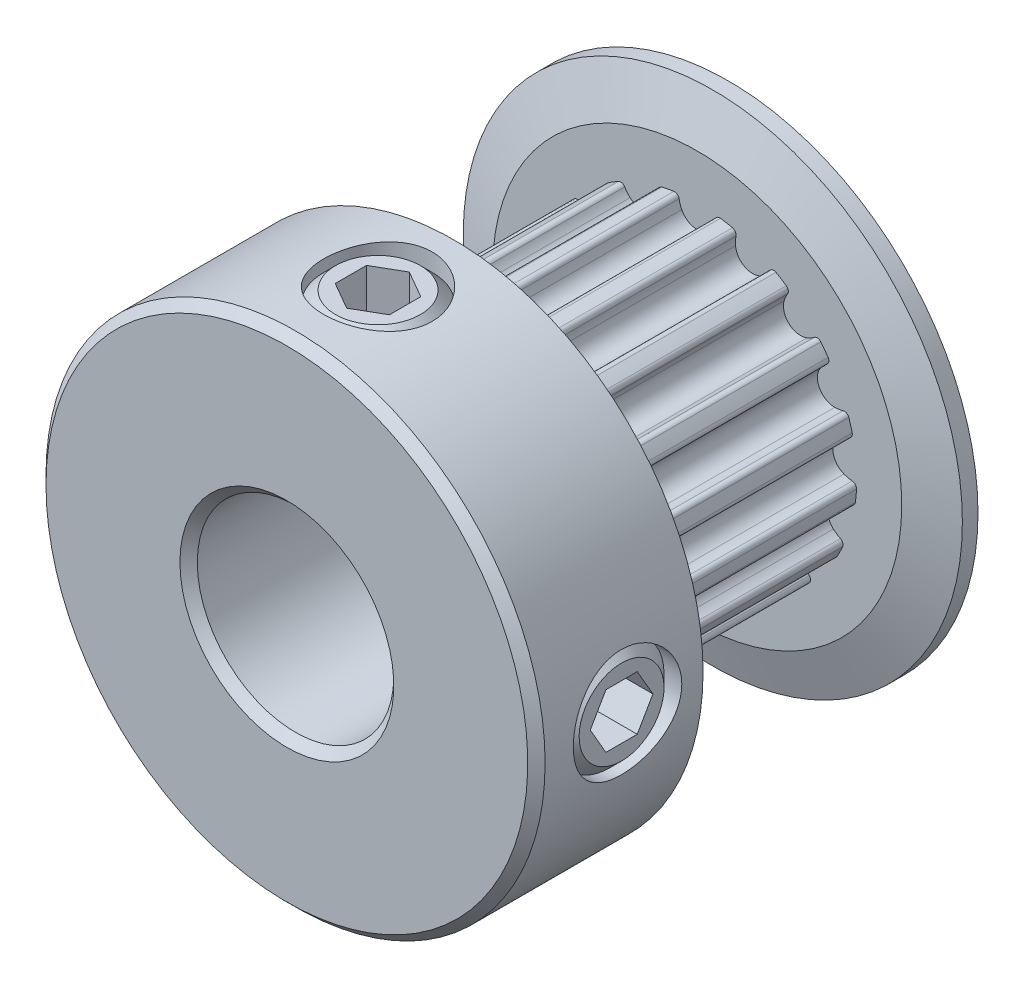
SolidWorks part; units mm, degrees
ref_plane "Front Plane" through (0, 0, 0) normal (0, 0, 1) x (1, 0, 0)
ref_plane "Top Plane" through (0, 0, 0) normal (0, 1, 0) x (1, 0, 0)
ref_plane "Right Plane" through (0, 0, 0) normal (1, 0, 0) x (0, 0, -1)
sketch "Sketch1" plane through (0, 0, 0) normal (0, 0, 1) x (1, 0, 0)
  line L1 (-1.7182, 4.406) -> (1.7182, 4.406) construction
  line L4 (0, 0) -> (0, 4.406) construction
  line L5 (0, 4.406) -> (0, 10.5496) construction
  line L6 (0, 5.41) -> (1.9655, 5.0403) construction
  line L7 (1.9655, 5.0403) -> (2.5999, 4.793) construction
  line L8 (1.9655, 5.0403) -> (1.7182, 4.406) construction
  line L9 (-1.9655, 5.0403) -> (-1.7182, 4.406) construction
  line L10 (-1.8733, 4.8037) -> (-3.1449, 8.0645)
  line L11 (-3.1449, 8.0645) -> (3.1449, 8.0645)
  line L12 (3.1449, 8.0645) -> (1.8733, 4.8037)
  circle A0 centre (0, 0) radius 5.41 construction
  circle A1 centre (0, 0) radius 8.0645 construction
  circle A2 centre (0, 0) radius 5.156 construction
  arc A3 (-0.4989, 4.7178) -> (0.4989, 4.7178) centre (0, 4.961) ccw
  arc A4 (-0.4989, 4.7178) -> (-0.5842, 4.9788) centre (0.4, 5.156) cw
  arc A5 (-1.8733, 4.8037) -> (-0.7537, 5.1006) centre (0, 0) cw
  arc A6 (-0.5842, 4.9788) -> (-0.7537, 5.1006) centre (-0.7318, 4.9522) ccw
  arc A7 (1.8733, 4.8037) -> (0.7537, 5.1006) centre (0, 0) ccw
  arc A8 (0.5842, 4.9788) -> (0.7537, 5.1006) centre (0.7318, 4.9522) cw
  arc A9 (0.4989, 4.7178) -> (0.5842, 4.9788) centre (-0.4, 5.156) ccw
  point P6 (0, 20.9083)
  point P11 (0, 5.41)
  point P13 (0, 8.0645)
  point P14 (0, 5.156)
  dimension "D1" = 10.3587
  dimension "D2" = 5.1396
sketch "Sketch2" plane through (0, 0, 0) normal (1, 0, 0) x (0, 0, -1)
  line L0 (-7.135, 3.175) -> (7.135, 3.175)
  line L1 (-7.135, 3.175) -> (-7.135, 8.0645)
  line L2 (-1.75, 8.0645) -> (-7.135, 8.0645)
  line L3 (-2.255, 3.175) -> (-2.255, 8.0645) construction
  line L4 (-2.255, 8.0645) -> (-1.245, 8.0645) construction
  line L5 (-1.245, 8.0645) -> (-1.245, 5.156) construction
  line L6 (-1.245, 5.156) -> (6.125, 5.156)
  line L7 (6.125, 5.156) -> (6.125, 8.0645) construction
  line L8 (6.125, 8.0645) -> (7.135, 8.0645) construction
  line L9 (7.135, 8.0645) -> (7.135, 3.175)
  line L10 (-7.135, 0) -> (7.135, 0) construction
  line L11 (6.63, 8.0645) -> (6.125, 6.6102)
  line L12 (-1.245, 6.6102) -> (-1.75, 8.0645)
  line L14 (-1.245, 6.6102) -> (-1.245, 5.156)
  line L15 (6.125, 5.156) -> (6.125, 6.6102)
  line L16 (6.63, 8.0645) -> (7.135, 8.0645)
  arc A0 (-1.245, 6.6102) -> (-1.75, 8.0645) centre (-3.5914, 6.6102) ccw construction
  arc A1 (6.125, 6.6102) -> (6.63, 8.0645) centre (8.4714, 6.6102) cw construction
  point P12 (-1.245, 6.6102)
  point P14 (-1.75, 8.0645)
  point P20 (6.125, 6.6102)
  point P21 (6.63, 8.0645)
  point P25 (6.125, 0)
  point P26 (-1.245, 0)
  dimension "OA" = 14.27
  dimension "Bore" = 6.35
  dimension "Outside Width" = 8.38
  dimension "Inside Width" = 7.37
revolve "Revolve1" add sketch "Sketch2" angle 360 mid plane about L10
sketch "Sketch3" plane through (0, 0, 0) normal (0, 0, 1) x (1, 0, 0)
  line L6 (3.1449, 8.0645) -> (-3.1449, 8.0645)
  line L7 (1.8733, 4.8037) -> (3.1449, 8.0645)
  line L8 (-3.1449, 8.0645) -> (-1.8733, 4.8037)
  line L9 (3.1449, 8.0645) -> (-3.1449, 8.0645)
  line L10 (1.8733, 4.8037) -> (3.1449, 8.0645)
  line L11 (-3.1449, 8.0645) -> (-1.8733, 4.8037)
  arc A8 (1.8733, 4.8037) -> (0.7537, 5.1006) centre (0, 0) ccw
  arc A9 (0.7537, 5.1006) -> (0.5842, 4.9788) centre (0.7318, 4.9522) ccw
  arc A10 (0.4989, 4.7178) -> (0.5842, 4.9788) centre (-0.4, 5.156) ccw
  arc A11 (-0.4989, 4.7178) -> (0.4989, 4.7178) centre (0, 4.961) ccw
  arc A12 (-0.5842, 4.9788) -> (-0.4989, 4.7178) centre (0.4, 5.156) ccw
  arc A13 (-0.5842, 4.9788) -> (-0.7537, 5.1006) centre (-0.7318, 4.9522) ccw
  arc A14 (-0.7537, 5.1006) -> (-1.8733, 4.8037) centre (0, 0) ccw
  arc A15 (1.8733, 4.8037) -> (0.7537, 5.1006) centre (0, 0) ccw
  arc A16 (0.7537, 5.1006) -> (0.5842, 4.9788) centre (0.7318, 4.9522) ccw
  arc A17 (0.4989, 4.7178) -> (0.5842, 4.9788) centre (-0.4, 5.156) ccw
  arc A18 (-0.4989, 4.7178) -> (0.4989, 4.7178) centre (0, 4.961) ccw
  arc A19 (-0.5842, 4.9788) -> (-0.4989, 4.7178) centre (0.4, 5.156) ccw
  arc A20 (-0.5842, 4.9788) -> (-0.7537, 5.1006) centre (-0.7318, 4.9522) ccw
  arc A21 (-0.7537, 5.1006) -> (-1.8733, 4.8037) centre (0, 0) ccw
  dimension "D1" = 0
extrude "Cut-Extrude1" cut sketch "Sketch3" against normal up to vertex (6.125 mm away) from vertex up to point (0, 5.156, -6.125) starting at point (0, 5.156, 1.245)
pattern_circular "CirPattern1" count 17 over 360 about axis through (0, 0, 7.135) along (0, 0, 1) of "Cut-Extrude1"
sketch "Sketch4" plane through (0, 0, 0) normal (1, 0, 0) x (0, -1, 0)
  line L0 (0, -1.245) -> (0, -7.135) construction
  line L1 (-3.175, -7.135) -> (3.175, -7.135) construction
  line L2 (6.6102, -1.245) -> (-6.6102, -1.245) construction
  circle A0 centre (0, -4.19) radius 1.7526
extrude "Cut-Extrude2" cut sketch "Sketch4" along normal through all
ref_plane "Plane1" through (0, 0, 4.19) normal (0, 0, 1) x (1, 0, 0)
sketch "Sketch5" plane through (0, 0, 4.19) normal (0, 0, 1) x (1, 0, 0)
  line L0 (0, 0) -> (0, 8.0645) construction
  line L1 (3.175, -1.3716) -> (3.175, 0)
  line L2 (3.556, -1.7526) -> (7.4908, -1.7526)
  line L3 (3.175, 0) -> (8.0645, 0) construction
  line L4 (3.175, 0) -> (7.8718, 0)
  line L5 (7.8718, 0) -> (7.8718, -1.3716)
  line L6 (3.556, -1.7526) -> (3.175, -1.3716)
  line L7 (7.8718, -1.3716) -> (7.4908, -1.7526)
  circle A0 centre (0, 0) radius 8.0645 construction
  circle A1 centre (0, 0) radius 3.175 construction
  point P2 (3.175, -1.7526)
  point P11 (7.8718, -1.7526)
revolve "Revolve2" add sketch "Sketch5" angle 360 mid plane about L4
sketch "Sketch6" plane through (7.8718, 5.3841, 0) normal (-1, 0, 0) x (0, -1, 0)
  line L1 (5.3841, 5.2019) -> (4.5078, 4.6959)
  line L2 (4.5078, 4.6959) -> (4.5078, 3.6841)
  line L3 (4.5078, 3.6841) -> (5.3841, 3.1781)
  line L4 (5.3841, 3.1781) -> (6.2604, 3.6841)
  line L5 (6.2604, 3.6841) -> (6.2604, 4.6959)
  line L6 (6.2604, 4.6959) -> (5.3841, 5.2019)
  circle A0 centre (5.3841, 4.19) radius 0.8763 construction
  dimension "D1" = 1.7526
extrude "Cut-Extrude3" cut sketch "Sketch6" along normal blind 1.3144
pattern_circular "CirPattern3" count 2 over 90 about axis through (0, 0, 7.135) along (0, 0, 1) of "Cut-Extrude2", "Revolve2", "Cut-Extrude3"
chamfer "Chamfer1" distance 0.2807 angle 45 2 edges at (3.175, 0, 7.135) (8.0645, 0, 7.135)
ref_axis "Center Axis 1" through (0, 0, -7.135) along (0, 0, 1)
ref_plane "Contact Plane 1" through (0, 0, 7.135) normal (0, 0, 1) x (1, 0, 0)
ref_plane "Contact Plane 2" through (0, 0, -7.135) normal (0, 0, -1) x (-1, 0, 0)
equation "\"D2@Sketch1\"= \"D1@Sketch1\" / 2"
equation "\"D1@Sketch6\" = \"Set Screw@Sketch4\" / 2"
equation "\"D1@Cut-Extrude3\" = \"D1@Sketch6\"*.75"
